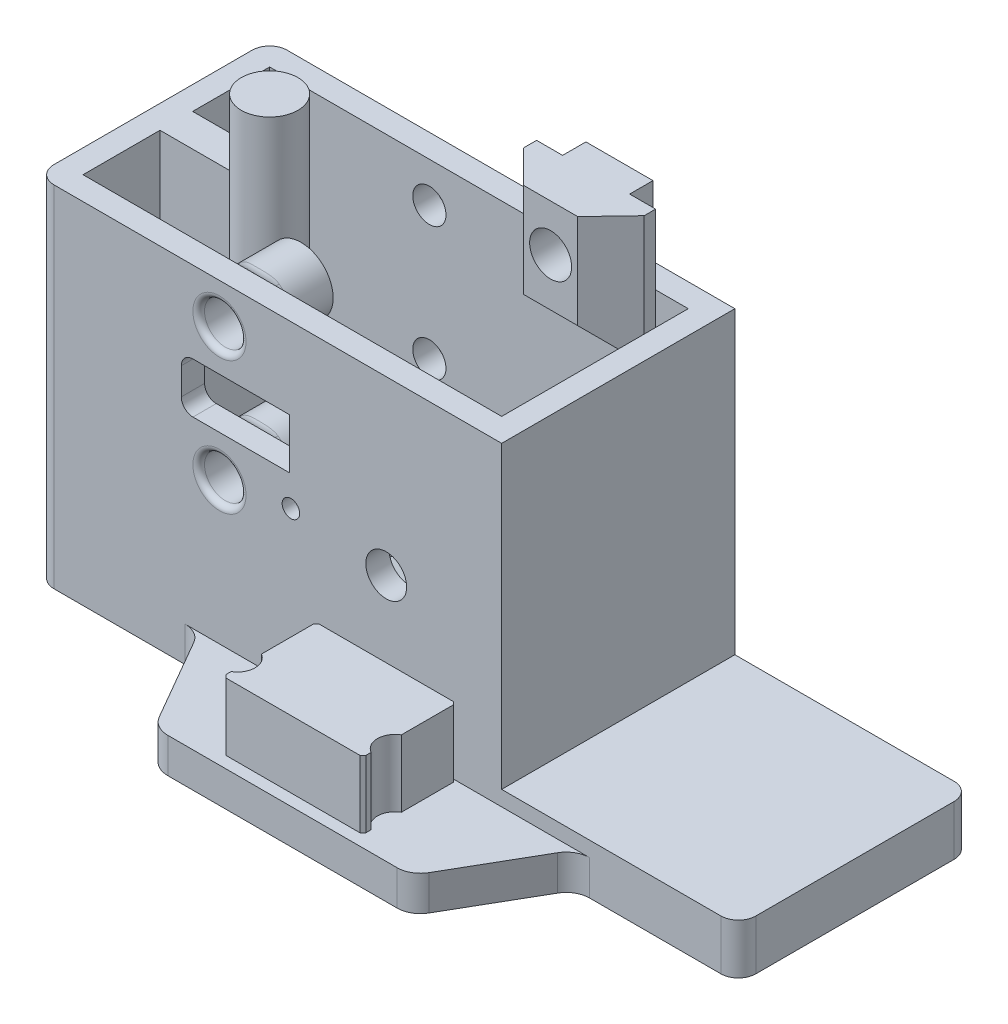
SolidWorks part; units mm, degrees
ref_plane "Front Plane" through (0, 0, 0) normal (0, 0, 1) x (1, 0, 0)
ref_plane "Top Plane" through (0, 0, 0) normal (0, 1, 0) x (1, 0, 0)
ref_plane "Right Plane" through (0, 0, 0) normal (1, 0, 0) x (0, 0, -1)
sketch "Sketch1" plane through (0, 0, 0) normal (0, 1, 0) x (1, 0, 0)
  line L0 (92.404, 9.1314) -> (130.804, 9.1314)
  line L1 (90.904, 27.6314) -> (90.904, 10.6314)
  line L2 (90.904, 19.1314) -> (130.804, 19.1314) construction
  line L3 (130.804, 19.1314) -> (130.804, 29.1314)
  line L4 (130.804, 19.1314) -> (130.804, 9.1314)
  line L5 (104.504, 29.1314) -> (97.4065, 29.1314)
  line L6 (117.304, 29.1314) -> (124.4015, 29.1314)
  line L16 (97.4065, 29.1314) -> (92.404, 29.1314)
  line L17 (97.4065, 28.7045) -> (97.4065, 29.1314) construction
  line L18 (97.829, 28.6971) -> (97.4065, 28.7045) construction
  line L19 (97.829, 27.3314) -> (97.829, 28.6971) construction
  line L20 (95.5994, 27.3314) -> (97.829, 27.3314) construction
  line L21 (95.5994, 26.0717) -> (95.5994, 27.3314) construction
  line L22 (98.4994, 23.0314) -> (95.5994, 26.0717) construction
  line L23 (103.3087, 23.0314) -> (98.4994, 23.0314) construction
  line L24 (106.2087, 25.9314) -> (103.3087, 23.0314) construction
  line L25 (106.2087, 27.3314) -> (106.2087, 25.9314) construction
  line L26 (103.979, 27.3314) -> (106.2087, 27.3314) construction
  line L27 (103.979, 28.6105) -> (103.979, 27.3314) construction
  line L28 (104.504, 28.6105) -> (103.979, 28.6105) construction
  line L29 (104.504, 29.1314) -> (104.504, 28.6105) construction
  line L30 (117.304, 29.1314) -> (104.504, 29.1314)
  line L31 (117.304, 28.6105) -> (117.304, 29.1314) construction
  line L32 (117.829, 28.6105) -> (117.304, 28.6105) construction
  line L33 (117.829, 27.3314) -> (117.829, 28.6105) construction
  line L34 (115.5994, 27.3314) -> (117.829, 27.3314) construction
  line L35 (115.5994, 25.9314) -> (115.5994, 27.3314) construction
  line L36 (118.4994, 23.0314) -> (115.5994, 25.9314) construction
  line L37 (123.3087, 23.0314) -> (118.4994, 23.0314) construction
  line L38 (126.2087, 26.0717) -> (123.3087, 23.0314) construction
  line L39 (126.2087, 27.3314) -> (126.2087, 26.0717) construction
  line L40 (123.979, 27.3314) -> (126.2087, 27.3314) construction
  line L41 (123.979, 28.6971) -> (123.979, 27.3314) construction
  line L42 (124.4015, 28.7045) -> (123.979, 28.6971) construction
  line L43 (124.4015, 29.1314) -> (124.4015, 28.7045) construction
  line L44 (130.804, 29.1314) -> (124.4015, 29.1314)
  line L92 (124.504, 9.6522) -> (124.504, 9.1314) construction
  line L93 (123.979, 9.6522) -> (124.504, 9.6522) construction
  line L94 (123.979, 10.9314) -> (123.979, 9.6522) construction
  line L95 (126.2087, 10.9313) -> (123.979, 10.9314) construction
  line L96 (126.2087, 12.3314) -> (126.2087, 10.9313) construction
  line L97 (123.3087, 15.2314) -> (126.2087, 12.3314) construction
  line L98 (118.4994, 15.2314) -> (123.3087, 15.2314) construction
  line L99 (115.5994, 12.191) -> (118.4994, 15.2314) construction
  line L100 (115.5994, 10.9314) -> (115.5994, 12.191) construction
  line L101 (117.829, 10.9314) -> (115.5994, 10.9314) construction
  line L102 (117.829, 9.5656) -> (117.829, 10.9314) construction
  line L103 (117.4065, 9.5582) -> (117.829, 9.5656) construction
  line L104 (117.4065, 9.1314) -> (117.4065, 9.5582) construction
  line L106 (104.4015, 9.5582) -> (104.4015, 9.1314) construction
  line L107 (103.979, 9.5656) -> (104.4015, 9.5582) construction
  line L108 (103.979, 10.9314) -> (103.979, 9.5656) construction
  line L109 (106.2087, 10.9314) -> (103.979, 10.9314) construction
  line L110 (106.2087, 12.191) -> (106.2087, 10.9314) construction
  line L111 (103.3087, 15.2314) -> (106.2087, 12.191) construction
  line L112 (98.4994, 15.2314) -> (103.3087, 15.2314) construction
  line L113 (95.5994, 12.3314) -> (98.4994, 15.2314) construction
  line L114 (95.5994, 10.9314) -> (95.5994, 12.3314) construction
  line L115 (97.829, 10.9314) -> (95.5994, 10.9314) construction
  line L116 (97.829, 9.6522) -> (97.829, 10.9314) construction
  line L117 (97.304, 9.6522) -> (97.829, 9.6522) construction
  line L118 (97.304, 9.1314) -> (97.304, 9.6522) construction
  arc A1 (90.904, 10.6314) -> (92.404, 9.1314) centre (92.404, 10.6314) ccw
  arc A2 (92.404, 29.1314) -> (90.904, 27.6314) centre (92.404, 27.6314) ccw
  circle A5 centre (120.904, 19.1314) radius 2.5 construction
  circle A6 centre (100.904, 19.1314) radius 2.5 construction
extrude "Boss-Extrude1" add sketch "Sketch1" along normal blind 3
sketch "Sketch2" plane through (0, 3, 0) normal (0, 1, 0) x (1, 0, 0)
  line L0 (98.474, 19.1314) -> (92.904, 19.1314) construction
  line L1 (110.854, 27.1314) -> (110.854, 17.7314) construction
  line L2 (98.9178, 20.5314) -> (92.904, 20.5314)
  line L3 (98.9178, 17.7314) -> (92.904, 17.7314)
  line L4 (98.474, 20.5314) -> (90.904, 20.5314) construction
  line L5 (98.474, 17.7314) -> (90.904, 17.7314) construction
  line L6 (128.804, 27.1314) -> (92.904, 27.1314)
  line L7 (92.904, 27.1314) -> (92.904, 20.5314)
  line L8 (92.904, 11.1314) -> (128.804, 11.1314)
  line L9 (128.804, 11.1314) -> (128.804, 17.7314)
  line L10 (92.404, 9.1314) -> (130.804, 9.1314)
  line L11 (130.804, 9.1314) -> (130.804, 29.1314)
  line L12 (130.804, 29.1314) -> (92.404, 29.1314)
  line L13 (90.904, 27.6314) -> (90.904, 10.6314)
  line L14 (92.404, 9.1314) -> (130.804, 9.1314)
  line L15 (130.804, 9.1314) -> (130.804, 29.1314)
  line L16 (130.804, 29.1314) -> (92.404, 29.1314)
  line L17 (90.904, 27.6314) -> (90.904, 10.6314)
  line L18 (98.474, 19.1314) -> (90.904, 19.1314) construction
  line L19 (92.904, 17.7314) -> (92.904, 11.1314)
  line L20 (92.904, 27.1314) -> (92.904, 11.1314) construction
  line L23 (128.804, 20.5314) -> (128.804, 27.1314)
  line L24 (128.804, 11.1314) -> (128.804, 27.1314) construction
  line L25 (128.804, 20.5314) -> (128.804, 17.7314)
  arc A0 (92.904, 27.1314) -> (92.904, 27.1314) centre (92.904, 27.1314) ccw
  arc A1 (98.9178, 17.7314) -> (98.9178, 20.5314) centre (100.904, 19.1314) ccw
  arc A2 (92.904, 11.1314) -> (92.904, 11.1314) centre (92.904, 11.1314) ccw
  arc A3 (90.904, 10.6314) -> (92.404, 9.1314) centre (92.404, 10.6314) ccw
  arc A4 (92.404, 29.1314) -> (90.904, 27.6314) centre (92.404, 27.6314) ccw
  arc A5 (90.904, 10.6314) -> (92.404, 9.1314) centre (92.404, 10.6314) ccw
  arc A6 (92.404, 29.1314) -> (90.904, 27.6314) centre (92.404, 27.6314) ccw
  dimension "D1" = 1.4
  dimension "D2" = 1.4
  dimension "D3" = 0
  dimension "D4" = 2
extrude "Boss-Extrude2" add sketch "Sketch2" along normal blind 27
sketch "Sketch3" plane through (0, 30, 0) normal (0, 1, 0) x (1, 0, 0)
  circle A0 centre (100.904, 19.1314) radius 2.43
  arc A3 (98.9178, 17.7314) -> (98.9178, 20.5314) centre (100.904, 19.1314) ccw construction
extrude "Boss-Extrude3" add sketch "Sketch3" along normal blind 6
sketch "Sketch4" plane through (0, 0, -9.1314) normal (0, 0, 1) x (1, 0, 0)
  line L1 (112.6131, 18.7146) -> (103.3294, 18.7146)
  line L2 (112.6131, 18.7146) -> (112.6131, 23.0283)
  line L3 (112.6131, 23.0283) -> (103.3294, 23.0283)
  line L4 (103.3294, 18.7146) -> (103.3294, 23.0283)
extrude "Cut-Extrude1" cut sketch "Sketch4" against normal blind 3
sketch "Sketch6" plane through (0, 0, -11.1314) normal (0, 0, -1) x (-1, 0, 0)
  circle A0 centre (-106.604, 26.575) radius 2.75
  circle A1 centre (-106.604, 15.175) radius 2.75
extrude "Boss-Extrude4" add sketch "Sketch6" along normal blind 5
sketch "Sketch7" plane through (0, 0, -9.1314) normal (0, 0, 1) x (1, 0, 0)
  circle A0 centre (106.604, 26.575) radius 1.78
  circle A1 centre (106.604, 15.175) radius 1.78
extrude "Cut-Extrude2" cut sketch "Sketch7" against normal blind 3
sketch "Sketch8" plane through (0, 0, -16.1314) normal (0, 0, -1) x (-1, 0, 0)
  circle A0 centre (-106.604, 15.175) radius 1.5
  circle A1 centre (-106.604, 26.575) radius 1.5
extrude "Cut-Extrude3" cut sketch "Sketch8" against normal blind 6
fillet "Fillet2" radius 1.5 2 edges at (103.854, 15.175, -11.1314) (103.854, 26.575, -11.1314)
fillet "Fillet3" radius 0.5 2 edges at (108.384, 15.175, -9.1314) (108.384, 26.575, -9.1314)
sketch "Sketch9" plane through (0, 0, -29.1314) normal (0, 0, -1) x (-1, 0, 0)
  circle A2 centre (-106.604, 15.175) radius 1.425
  circle A3 centre (-106.604, 26.575) radius 1.425
extrude "Cut-Extrude4" cut sketch "Sketch9" against normal blind 6
sketch "Sketch11" plane through (0, 0, -27.1314) normal (0, 0, 1) x (1, 0, 0)
  line L0 (103.334, 3) -> (103.334, 36) construction
  line L1 (92.904, 3) -> (103.334, 3)
  line L2 (92.904, 3) -> (92.904, 22)
  line L3 (92.904, 22) -> (103.334, 22)
  line L4 (103.334, 3) -> (103.334, 22)
  line L5 (98.9178, 30) -> (92.904, 30) construction
  dimension "D1" = 8
extrude "Cut-Extrude5" cut sketch "Sketch11" along normal blind 11
chamfer "Chamfer1" distance 11 angle 45 1 edges at (92.904, 22, -19.1314)
sketch "Sketch12" plane through (0, 0, -9.1314) normal (0, 0, 1) x (1, 0, 0)
  circle A0 centre (120.904, 15.25) radius 1.75
extrude "Cut-Extrude6" cut sketch "Sketch12" against normal blind 3
sketch "Sketch13" plane through (0, 0, 0) normal (0, -1, 0) x (1, 0, 0)
  circle A0 centre (111.604, -19.1314) radius 3.125
extrude "Cut-Extrude7" cut sketch "Sketch13" against normal blind 4
sketch "Sketch14" plane through (0, 3, 0) normal (0, 1, 0) x (1, 0, 0)
  line L1 (111.604, 23.8656) -> (107.504, 21.4985)
  line L2 (107.504, 21.4985) -> (107.504, 16.7642)
  line L3 (107.504, 16.7642) -> (111.604, 14.3971)
  line L4 (111.604, 14.3971) -> (115.704, 16.7642)
  line L5 (115.704, 16.7642) -> (115.704, 21.4985)
  line L6 (115.704, 21.4985) -> (111.604, 23.8656)
  circle A0 centre (111.604, 19.1314) radius 4.1 construction
  circle A1 centre (111.604, 19.1314) radius 6
  dimension "D1" = 8.2
extrude "Boss-Extrude5" add sketch "Sketch14" along normal blind 2
fillet "Fillet4" radius 2 1 edges at (111.604, 3, -13.1314)
sketch "Sketch18" plane through (0, 36, 0) normal (0, 1, 0) x (1, 0, 0)
  line L0 (128.804, 27.1314) -> (92.904, 27.1314) construction
  line L1 (128.804, 27.1314) -> (111.604, 27.1314) construction
  line L2 (130.804, 29.1314) -> (92.404, 29.1314) construction
  line L20 (118.029, 29.1314) -> (118.029, 27.1314)
  line L21 (118.029, 27.1314) -> (115.7994, 27.1314)
  line L22 (115.7994, 27.1314) -> (115.7994, 26.0142)
  line L23 (115.7994, 26.0142) -> (118.5822, 23.2314)
  line L24 (118.5822, 23.2314) -> (123.223, 23.2314)
  line L25 (123.223, 23.2314) -> (126.0087, 26.1518)
  line L26 (126.0087, 26.1518) -> (126.0087, 27.1314)
  line L27 (126.0087, 27.1314) -> (123.779, 27.1314)
  line L28 (123.779, 27.1314) -> (123.779, 29.1314)
  line L29 (123.779, 29.1314) -> (118.029, 29.1314)
extrude "Boss-Extrude16" add sketch "Sketch18" against normal blind 8
chamfer "Chamfer2" distance 4 angle 45 1 edges at (120.904, 28, -27.1314)
sketch "Sketch19" plane through (0, 0, -29.1314) normal (0, 0, -1) x (-1, 0, 0)
  line L0 (-123.779, 36) -> (-118.029, 30) construction
sketch "Sketch20" plane through (0, 0, -23.2314) normal (0, 0, 1) x (1, 0, 0)
  line L1 (118.5822, 36) -> (123.223, 36) construction
  circle A0 centre (120.904, 32) radius 1.8
  circle A1 centre (120.904, 32) radius 2.12 construction
  point P5 (120.9026, 36)
  dimension "D1" = 3.6
  dimension "D2" = 4
extrude "Cut-Extrude10" cut sketch "Sketch20" against normal blind 3.1
sketch "Sketch21" plane through (0, 0, -26.3314) normal (0, 0, 1) x (1, 0, 0)
  circle A0 centre (120.904, 32) radius 1.5
extrude "Cut-Extrude11" cut sketch "Sketch21" against normal blind 3.1
sketch "Sketch22" plane through (0, 0, -11.1314) normal (0, 0, -1) x (-1, 0, 0)
  line L1 (-120.904, 18.4543) -> (-123.679, 16.8521)
  line L2 (-123.679, 16.8521) -> (-123.679, 13.6479)
  line L3 (-123.679, 13.6479) -> (-120.904, 12.0457)
  line L4 (-120.904, 12.0457) -> (-118.129, 13.6479)
  line L5 (-118.129, 13.6479) -> (-118.129, 16.8521)
  line L6 (-118.129, 16.8521) -> (-120.904, 18.4543)
  circle A0 centre (-120.904, 15.25) radius 2.775 construction
  circle A1 centre (-120.904, 15.25) radius 4.35
  dimension "D1" = 5.55
extrude "Boss-Extrude17" add sketch "Sketch22" along normal blind 2.6
fillet "Fillet5" radius 2.6 1 edges at (116.554, 15.25, -11.1314)
sketch "Sketch23" plane through (130.804, 0, 0) normal (1, 0, 0) x (0, 0, -1)
  line L0 (9.1314, 30) -> (9.1314, 0) construction
  line L1 (29.1314, 0) -> (9.1314, 0)
  line L2 (29.1314, 0) -> (29.1314, 4.3)
  line L3 (29.1314, 4.3) -> (9.1314, 4.3)
  line L4 (9.1314, 0) -> (9.1314, 4.3)
  dimension "D1" = 4.3
extrude "Boss-Extrude18" add sketch "Sketch23" along normal blind 20.3
fillet "Fillet6" radius 1.5 2 edges at (151.104, 2.15, -29.1314) (151.104, 2.15, -9.1314)
sketch "Sketch25" plane through (0, 0, 0) normal (0, -1, 0) x (1, 0, 0)
  line L0 (131.9922, -0.1314) -> (137.1884, -9.1314)
  line L1 (121.004, -9.1314) -> (121.004, -0.1314) construction
  line L3 (108.884, -9.1314) -> (131.9589, -9.1314) construction
  line L4 (92.404, -9.1314) -> (149.604, -9.1314) construction
  line L5 (110.0158, -0.1314) -> (131.9922, -0.1314)
  line L6 (137.1884, -9.1314) -> (104.8197, -9.1314)
  line L7 (133.124, -9.1314) -> (110.0491, -9.1314) construction
  line L8 (110.0158, -0.1314) -> (104.8197, -9.1314)
  dimension "D1" = 120
extrude "Boss-Extrude20" add sketch "Sketch25" against normal blind 3
fillet "Fillet7" radius 2 4 edges at (137.1884, 1.5, -9.1314) (104.8197, 1.5, -9.1314) (110.0158, 1.5, -0.1314) (131.9922, 1.5, -0.1314)
sketch "Sketch28" plane through (0, 3, 0) normal (0, 1, 0) x (1, 0, 0)
  line L20 (126.904, 1.3814) -> (126.904, 1.8323)
  line L21 (126.904, 4.4304) -> (126.904, 8.8814)
  line L22 (126.904, 8.8814) -> (126.654, 9.1314)
  line L23 (126.654, 9.1314) -> (115.154, 9.1314)
  line L24 (115.154, 9.1314) -> (114.904, 8.8814)
  line L25 (114.904, 8.8814) -> (114.904, 4.4304)
  line L26 (114.904, 1.8323) -> (114.904, 1.3814)
  line L27 (114.904, 1.3814) -> (115.154, 1.1314)
  line L28 (115.154, 1.1314) -> (126.654, 1.1314)
  line L29 (126.654, 1.1314) -> (126.904, 1.3814)
  arc A12 (126.654, 2.0133) -> (126.904, 1.8323) centre (127.654, 3.1314) ccw
  arc A13 (126.654, 4.2494) -> (126.654, 2.0133) centre (127.654, 3.1314) ccw
  arc A14 (126.904, 4.4304) -> (126.654, 4.2494) centre (127.654, 3.1314) ccw
  arc A15 (115.154, 4.2494) -> (114.904, 4.4304) centre (114.154, 3.1314) ccw
  arc A16 (115.154, 2.0133) -> (115.154, 4.2494) centre (114.154, 3.1314) ccw
  arc A17 (114.904, 1.8323) -> (115.154, 2.0133) centre (114.154, 3.1314) ccw
extrude "Boss-Extrude21" add sketch "Sketch28" along normal blind 5.75
sketch "Sketch29" plane through (0, 0, -9.1314) normal (0, 0, 1) x (1, 0, 0)
  line L8 (113.454, 16.62) -> (112.004, 16.62) construction
  line L9 (112.004, 16.62) -> (112.004, 15.62) construction
  line L10 (112.004, 15.62) -> (113.454, 15.62) construction
  line L11 (113.454, 15.62) -> (113.454, 16.62) construction
  circle A0 centre (112.729, 16.12) radius 0.75
extrude "Cut-Extrude12" cut sketch "Sketch29" against normal blind 3
fillet "Fillet8" radius 1 2 edges at (103.3294, 23.0283, -10.1314) (103.3294, 18.7146, -10.1314)
